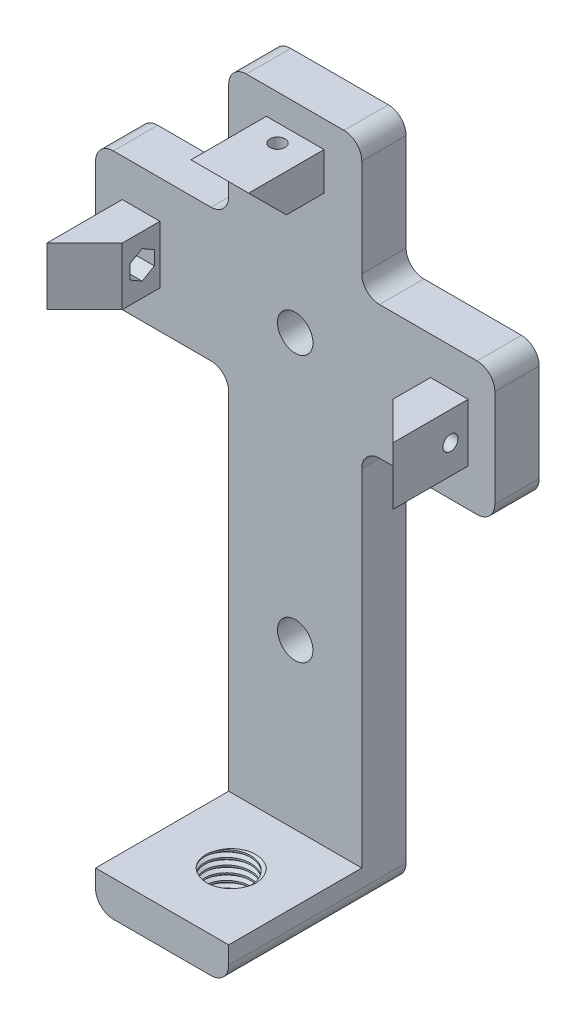
SolidWorks part; units mm, degrees
ref_plane "Płaszczyzna przednia" through (0, 0, 0) normal (0, 0, 1) x (1, 0, 0)
ref_plane "Płaszczyzna górna" through (0, 0, 0) normal (0, 1, 0) x (1, 0, 0)
ref_plane "Płaszczyzna prawa" through (0, 0, 0) normal (1, 0, 0) x (0, 0, -1)
sketch "Sketch1" plane through (0, 0, 0) normal (0, 0, 1) x (1, 0, 0)
  line L0 (-15, 15) -> (-15, 45)
  line L1 (-45, -45) -> (45, -45) construction
  line L2 (-45, -45) -> (-45, 45) construction
  line L3 (-45, 45) -> (45, 45) construction
  line L4 (45, -45) -> (45, 45) construction
  line L5 (-45, -45) -> (45, 45) construction
  line L6 (-45, 45) -> (45, -45) construction
  line L7 (-15, -45) -> (15, -45)
  line L8 (-15, -45) -> (-15, -15)
  line L9 (-15, 45) -> (15, 45)
  line L10 (15, -45) -> (15, -15)
  line L11 (15, -15) -> (45, -15)
  line L12 (15, 15) -> (15, 45)
  line L13 (-45, -15) -> (-15, -15)
  line L14 (-45, -15) -> (-45, 15)
  line L15 (-45, 15) -> (-15, 15)
  line L16 (45, -15) -> (45, 15)
  line L17 (15, 15) -> (45, 15)
  point P0 (0, 0)
  point P6 (0, 0)
  point P11 (0, 0)
  dimension "D1" = 30
  dimension "D2" = 30
  dimension "D3" = 30
  dimension "D4" = 30
  dimension "D5" = 90
  dimension "D6" = 90
extrude "Boss-Extrude1" add sketch "Sketch1" along normal blind 10
sketch "Sketch3" plane through (0, 0, 10) normal (0, 0, 1) x (1, 0, 0)
  line L0 (0, 0) -> (39, 0) construction
  line L1 (0, 0) -> (-39, 0) construction
  line L2 (0, 0) -> (0, 39) construction
  line L3 (-39, 0) -> (-37.5, 0) construction
  line L5 (-36, -6.5) -> (-39, -6.5)
  line L6 (-36, -6.5) -> (-36, 6.5)
  line L7 (-36, 6.5) -> (-39, 6.5)
  line L8 (-39, -6.5) -> (-39, 6.5)
  line L9 (-36, -6.5) -> (-39, 6.5) construction
  line L10 (-36, 6.5) -> (-39, -6.5) construction
  line L11 (36, -6.5) -> (39, -6.5)
  line L12 (36, -6.5) -> (36, 6.5)
  line L13 (36, 6.5) -> (39, 6.5)
  line L14 (39, -6.5) -> (39, 6.5)
  line L15 (36, -6.5) -> (39, 6.5) construction
  line L16 (36, 6.5) -> (39, -6.5) construction
  line L17 (-6.5, 36) -> (6.5, 36)
  line L18 (-6.5, 36) -> (-6.5, 39)
  line L19 (-6.5, 39) -> (6.5, 39)
  line L20 (6.5, 36) -> (6.5, 39)
  line L21 (-6.5, 36) -> (6.5, 39) construction
  line L22 (-6.5, 39) -> (6.5, 36) construction
  point P10 (0, 37.5)
  point P11 (37.5, 0)
  point P12 (37.5, 0)
  point P17 (0, 37.5)
  dimension "D1" = 1.5
  dimension "D2" = 3
  dimension "D3" = 13
  dimension "D4" = 39
  dimension "D5" = 39
  dimension "D6" = 39
  dimension "D7" = 1.5
  dimension "D8" = 1.5
  dimension "D9" = 3
  dimension "D10" = 13
  dimension "D11" = 3
  dimension "D12" = 13
extrude "Boss-Extrude2" add sketch "Sketch3" along normal blind 14
sketch "Sketch4" plane through (0, 6.5, 0) normal (0, 1, 0) x (1, 0, 0)
  line L0 (-39, -24) -> (-36, -21)
  line L1 (-39, -10) -> (-30.5, -10) construction
  line L2 (-39, -10) -> (-39, -24) construction
  line L3 (-39, -24) -> (-25, -24) construction
  line L4 (-25, -10) -> (-25, -24) construction
  line L5 (-39, -10) -> (-25, -24) construction
  line L6 (-39, -24) -> (-36, -21) construction
  line L7 (-39, -24) -> (-39, -27) construction
  line L8 (-39, -27) -> (-30.5, -18.5)
  line L11 (-39, -24) -> (-39, -27)
  line L12 (45, -10) -> (15, -10) construction
  line L13 (39, -24) -> (25, -24) construction
  line L14 (39, -24) -> (39, -10) construction
  line L15 (39, -10) -> (25, -10) construction
  line L16 (25, -24) -> (25, -10) construction
  line L17 (39, -24) -> (36, -21) construction
  line L18 (39, -10) -> (25, -24) construction
  line L20 (39, -24) -> (39, -27)
  line L21 (39, -27) -> (30.5, -18.5)
  line L23 (-30.5, -18.5) -> (-30.5, -10)
  line L24 (-30.5, -10) -> (-36, -10)
  line L25 (-36, -10) -> (-36, -21)
  line L26 (-36, -24) -> (-36, -10) construction
  line L27 (30.5, -18.5) -> (30.5, -10)
  line L28 (30.5, -10) -> (36, -10)
  line L29 (36, -10) -> (36, -21)
  line L30 (36, -24) -> (36, -10) construction
  line L32 (36, -21) -> (39, -24)
  point P4 (-32, -17)
  point P14 (32, -17)
  dimension "D1" = 14
  dimension "D2" = 14
  dimension "D3" = 14
extrude "Boss-Extrude3" add sketch "Sketch4" against normal blind 13
sketch "Sketch6" plane through (-6.5, 0, 0) normal (-1, 0, 0) x (0, 0, 1)
  line L0 (10, 45) -> (10, 15) construction
  line L1 (24, 39) -> (10, 39) construction
  line L2 (24, 39) -> (24, 25) construction
  line L3 (24, 25) -> (10, 25) construction
  line L4 (10, 39) -> (10, 25) construction
  line L5 (24, 39) -> (21, 36) construction
  line L6 (24, 25) -> (10, 39) construction
  line L7 (21, 36) -> (24, 39)
  line L8 (24, 39) -> (27, 39)
  line L11 (18.5, 30.5) -> (10, 30.5)
  line L12 (10, 30.5) -> (10, 36)
  line L13 (10, 36) -> (21, 36)
  line L14 (24, 36) -> (10, 36) construction
  line L15 (18.5, 30.5) -> (27, 39)
  point P4 (17, 32)
  dimension "D1" = 14
extrude "Boss-Extrude4" add sketch "Sketch6" against normal blind 13
sketch "Sketch7" plane through (0, 0, 0) normal (0, 0, -1) x (-1, 0, 0)
  line L0 (-15, -45) -> (15, -45)
  line L1 (-15, -45) -> (-15, -105)
  line L2 (15, -45) -> (15, -105)
  line L3 (-15, -105) -> (15, -105)
  dimension "D1" = 60
extrude "Boss-Extrude5" add sketch "Sketch7" against normal blind 10
sketch "Sketch8" plane through (0, 0, 0) normal (0, 0, -1) x (-1, 0, 0)
  line L0 (0, 0) -> (0, -60) construction
  circle A0 centre (0, 0) radius 4
  circle A1 centre (0, -60) radius 4
extrude "Cut-Extrude2" cut sketch "Sketch8" against normal blind 10
sketch "Sketch9" plane through (0, 0, 10) normal (0, 0, 1) x (1, 0, 0)
  line L0 (-15, -15) -> (-15, -105) construction
  line L1 (15, -105) -> (-15, -105)
  line L2 (15, -105) -> (15, -97)
  line L3 (15, -97) -> (-15, -97)
  line L4 (-15, -105) -> (-15, -97)
  line L5 (15, -105) -> (-15, -97) construction
  line L6 (15, -97) -> (-15, -105) construction
  point P4 (0, -101)
  dimension "D1" = 8
extrude "Boss-Extrude6" add sketch "Sketch9" along normal blind 30
sketch "Sketch10" plane through (0, -105, 0) normal (0, -1, 0) x (1, 0, 0)
  line L1 (-15, 40) -> (15, 40) construction
  line L2 (-15, 40) -> (-15, 10) construction
  line L3 (-15, 10) -> (15, 10) construction
  line L4 (15, 40) -> (15, 10) construction
  line L5 (-15, 40) -> (15, 10) construction
  line L6 (-15, 10) -> (15, 40) construction
  circle A0 centre (0, 25) radius 6
  point P4 (0, 25)
extrude "Cut-Extrude3" cut sketch "Sketch10" against normal blind 20
thread "Thread1" pitch 1.5 method extrude profile "Thread Profile1" start angle 0, offset 1, length 17, pitch 1.5, diameter 12
ref_plane "Plane1" through (6, -106, 25) normal (0, 0, 1) x (1, 0, 0)
sketch "Thread Profile1" plane through (6, -106, 25) normal (0, 0, 1) x (1, 0, 0)
  line L0 (0, 0) -> (0, 1.5) construction
  line L11 (0, 0) -> (0, 1.3125)
  line L12 (0, 1.3125) -> (-0.8119, 0.8437)
  line L13 (-0.8119, 0.8437) -> (-0.8119, 0.4687)
  line L15 (-0.8119, 0.4687) -> (0, 0)
  line L17 (-0.8119, 0.6562) -> (0, 0.6562) construction
  point P2 (0, 0)
  dimension "Pitch" = 1.5
  dimension "Profile_Angle" = 60
  dimension "Profile_Land" = 0.375
  dimension "Profile_Height" = 0.8119
sketch "Sketch15" plane through (0, 0, 40) normal (0, 0, 1) x (1, 0, 0)
  line L0 (15, -97) -> (15, -15) construction
  line L1 (-15, -97) -> (15, -97)
  line L2 (-15, -97) -> (-15, -72.1895)
  line L3 (-15, -72.1895) -> (15, -72.1895)
  line L4 (15, -97) -> (15, -72.1895)
  line L5 (-15, -97) -> (15, -72.1895) construction
  line L6 (-15, -72.1895) -> (15, -97) construction
  line L8 (15, -105) -> (-15, -105)
  line L9 (15, -105) -> (15, -109.5092)
  line L10 (15, -109.5092) -> (-15, -109.5092)
  line L11 (-15, -105) -> (-15, -109.5092)
  line L12 (15, -105) -> (-15, -109.5092) construction
  line L13 (15, -109.5092) -> (-15, -105) construction
  point P4 (0, -84.5947)
  point P12 (0, -107.2546)
extrude "Cut-Extrude4" cut sketch "Sketch15" against normal blind 25
sketch "Sketch17" plane through (-39, 0, 0) normal (-1, 0, 0) x (0, 0, 1)
  line L0 (27, -6.5) -> (10, -6.5) construction
  line L1 (10, 6.5) -> (18, 6.5) construction
  line L2 (10, 6.5) -> (10, -6.5) construction
  line L3 (10, -6.5) -> (18, -6.5) construction
  line L4 (18, 6.5) -> (18, -6.5) construction
  line L5 (10, 6.5) -> (18, -6.5) construction
  line L6 (10, -6.5) -> (18, 6.5) construction
  circle A0 centre (14, 0) radius 1.7
  point P4 (14, 0)
  dimension "D1" = 8
extrude "Cut-Extrude5" cut sketch "Sketch17" against normal blind 94
sketch "Sketch18" plane through (-30.5, 0, 0) normal (1, 0, 0) x (0, 0, -1)
  line L0 (-14, 0) -> (-12.625, 2.3816) construction
  line L1 (-14, 3.1754) -> (-16.75, 1.5877)
  line L2 (-16.75, 1.5877) -> (-16.75, -1.5877)
  line L3 (-16.75, -1.5877) -> (-14, -3.1754)
  line L4 (-14, -3.1754) -> (-11.25, -1.5877)
  line L5 (-11.25, -1.5877) -> (-11.25, 1.5877)
  line L6 (-11.25, 1.5877) -> (-14, 3.1754)
  circle A0 centre (-14, 0) radius 3.1754 construction
  dimension "D1" = 2.75
extrude "Cut-Extrude6" cut sketch "Sketch18" against normal blind 4.5 and the other way blind 65.5
sketch "Sketch19" plane through (0, 39, 0) normal (0, 1, 0) x (1, 0, 0)
  line L0 (6.5, -27) -> (6.5, -10) construction
  line L1 (-6.5, -10) -> (6.5, -10) construction
  line L2 (-6.5, -10) -> (-6.5, -18) construction
  line L3 (-6.5, -18) -> (6.5, -18) construction
  line L4 (6.5, -10) -> (6.5, -18) construction
  line L5 (-6.5, -10) -> (6.5, -18) construction
  line L6 (-6.5, -18) -> (6.5, -10) construction
  circle A0 centre (0, -14) radius 1.7
  point P4 (0, -14)
  dimension "D1" = 8
extrude "Cut-Extrude7" cut sketch "Sketch19" against normal blind 10.5
sketch "Sketch21" plane through (0, 30.5, 0) normal (0, -1, 0) x (-1, 0, 0)
  line L0 (0, -14) -> (-2.3816, -12.625) construction
  line L1 (-3.1754, -14) -> (-1.5877, -16.75)
  line L2 (-1.5877, -16.75) -> (1.5877, -16.75)
  line L3 (1.5877, -16.75) -> (3.1754, -14)
  line L4 (3.1754, -14) -> (1.5877, -11.25)
  line L5 (1.5877, -11.25) -> (-1.5877, -11.25)
  line L6 (-1.5877, -11.25) -> (-3.1754, -14)
  circle A0 centre (0, -14) radius 3.1754 construction
  dimension "D1" = 2.75
extrude "Cut-Extrude8" cut sketch "Sketch21" against normal blind 4.5
fillet "Fillet1" radius 4 12 edges at (-15, 45, 5) (15, 45, 5) (15, 15, 5) (-15, 15, 5) (-45, -15, 5) (-45, 15, 5) (45, 15, 5) (45, -15, 5) (15, -15, 5) (-15, -15, 5) (-15, -105, 20) (15, -105, 20)
